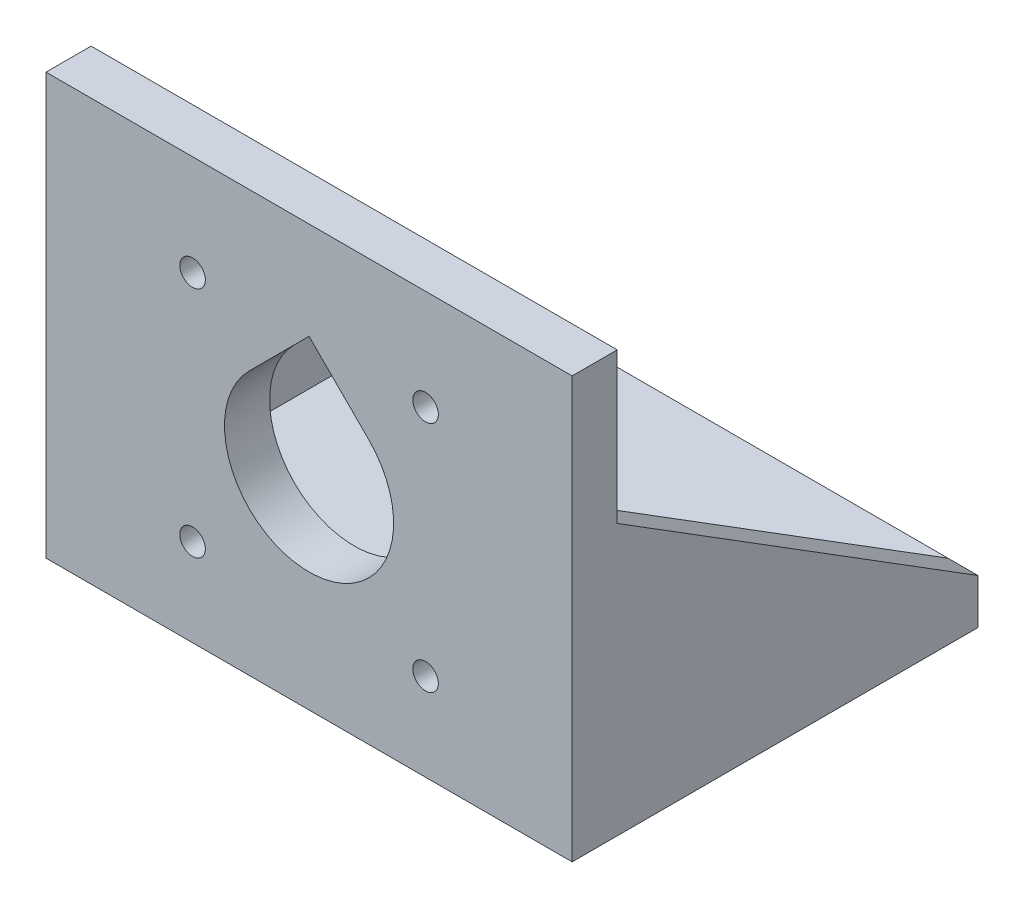
SolidWorks part; units mm, degrees
ref_plane "Спереди" through (0, 0, 0) normal (0, 0, 1) x (1, 0, 0)
ref_plane "Сверху" through (0, 0, 0) normal (0, 1, 0) x (1, 0, 0)
ref_plane "Справа" through (0, 0, 0) normal (1, 0, 0) x (0, 0, -1)
other "Configuration Table"
sketch "01_Пластина_эскиз" plane through (0, 0, 0) normal (0, 0, 1) x (1, 0, 0)
  line L1 (0, 0) -> (70, 0)
  line L2 (0, 0) -> (0, 56)
  line L3 (0, 56) -> (70, 56)
  line L4 (70, 0) -> (70, 56)
  dimension "D1" = 70
  dimension "D2" = 56
extrude "01_Передняя_пластина" add sketch "01_Пластина_эскиз" along normal blind 6
sketch "02_Полка_эскиз" plane through (0, 0, 0) normal (0, 1, 0) x (1, 0, 0)
  line L1 (0, 48) -> (70, 48)
  line L2 (0, 48) -> (0, -6)
  line L3 (0, -6) -> (70, -6)
  line L4 (70, 48) -> (70, -6)
  dimension "D1" = 70
  dimension "D2" = 54
  dimension "D3" = 6
extrude "02_Полка" add sketch "02_Полка_эскиз" along normal blind 6
sketch "03_Косынка_левая_эскиз" plane through (0, 0, 0) normal (1, 0, 0) x (0, 0, -1)
  line L0 (48, 6) -> (0, 6)
  line L1 (0, 6) -> (0, 36)
  line L2 (0, 36) -> (48, 6)
  dimension "D3" = 6
  dimension "D1" = 48
  dimension "D2" = 30
extrude "03_Косынка_левая" add sketch "03_Косынка_левая_эскиз" along normal blind 4
sketch "04_Косынка_правая_эскиз" plane through (0, 0, 0) normal (1, 0, 0) x (0, 0, -1)
  line L0 (48, 6) -> (0, 6)
  line L1 (0, 6) -> (0, 36)
  line L2 (0, 36) -> (48, 6)
  dimension "D3" = 6
  dimension "D1" = 48
  dimension "D2" = 30
extrude "04_Косынка_правая" add sketch "04_Косынка_правая_эскиз" along normal blind 4 from offset 66
sketch "05_Мотор_передний_фланец_эскиз" plane through (0, 0, 0) normal (0, 0, 1) x (1, 0, 0)
  line L0 (4, 6) -> (66, 6) construction
  circle A0 centre (35, 27.15) radius 11.25
  circle A1 centre (19.5, 11.65) radius 1.7
  circle A2 centre (19.5, 42.65) radius 1.7
  circle A3 centre (50.5, 11.65) radius 1.7
  circle A4 centre (50.5, 42.65) radius 1.7
  dimension "D1" = 3.4
  dimension "D2" = 3.4
  dimension "D3" = 3.4
  dimension "D4" = 3.4
  dimension "D5" = 22.5
  dimension "D6" = 15.5
  dimension "D7" = 31
  dimension "D8" = 15.5
  dimension "D9" = 31
  dimension "D10" = 35
  dimension "D11" = 21.15
extrude "05_Буртик_и_4_отверстия_М3" cut sketch "05_Мотор_передний_фланец_эскиз" against normal through all and the other way through all
sketch "06_Свод_45град_эскиз" plane through (0, 0, 0) normal (0, 0, 1) x (1, 0, 0)
  line L0 (27.045, 35.105) -> (42.955, 35.105)
  line L1 (42.955, 35.105) -> (35, 43.0599)
  line L2 (35, 43.0599) -> (27.045, 35.105)
  circle A0 centre (35, 27.15) radius 11.25 construction
  point P4 (26.9318, 34.9901)
  dimension "D1" = 7.955
  dimension "D2" = 15.9099
  dimension "D3" = 7.955
  dimension "D4" = 35
extrude "06_Свод_отверстия_для_печати" cut sketch "06_Свод_45град_эскиз" against normal through all and the other way through all
sketch "07_Крепление_полки_эскиз" plane through (0, 0, 0) normal (0, 1, 0) x (1, 0, 0)
  circle A0 centre (8.5, 12) radius 2.25
  circle A1 centre (8.5, 38) radius 2.25
  circle A2 centre (61.5, 12) radius 2.25
  circle A3 centre (61.5, 38) radius 2.25
  dimension "D1" = 4.5
  dimension "D2" = 4.5
  dimension "D3" = 4.5
  dimension "D4" = 4.5
  dimension "D5" = 53
  dimension "D6" = 26
  dimension "D7" = 8.5
  dimension "D8" = 12
extrude "07_4_отверстия_М4" cut sketch "07_Крепление_полки_эскиз" against normal through all and the other way through all
equation "\"Ширина\"= 70"
equation "\"Высота пластины\"= 56"
equation "\"Толщина стенок\"= 6"
equation "\"Длина полки\"= 48"
equation "\"Толщина косынки\"= 4"
equation "\"Высота косынки\"= 30"
equation "\"Высота оси\"= 30"
equation "\"Шаг М3 ПРЕДВ\"= 31"
equation "\"Отверстие буртика\"= 22.5"
equation "\"Отверстия М3\"= 3.4"
equation "\"Отверстия М4\"= 4.5"
equation "\"Отступ М4 сбоку\"= 8.5"
equation "\"Ближний ряд М4\"= 12"
equation "\"Отступ М4 сзади\"= 10"
equation "\"D1@01_Пластина_эскиз\" = \"Ширина\""
equation "\"D2@01_Пластина_эскиз\" = \"Высота пластины\""
equation "\"D1@01_Передняя_пластина\" = \"Толщина стенок\""
equation "\"D1@02_Полка_эскиз\" = \"Ширина\""
equation "\"D2@02_Полка_эскиз\" = \"Длина полки\" + \"Толщина стенок\""
equation "\"D1@02_Полка\" = \"Толщина стенок\""
equation "\"D1@03_Косынка_левая_эскиз\" = \"Длина полки\""
equation "\"D2@03_Косынка_левая_эскиз\" = \"Высота косынки\""
equation "\"D1@03_Косынка_левая\" = \"Толщина косынки\""
equation "\"D1@04_Косынка_правая_эскиз\" = \"Длина полки\""
equation "\"D2@04_Косынка_правая_эскиз\" = \"Высота косынки\""
equation "\"D1@04_Косынка_правая\" = \"Толщина косынки\""
equation "\"D19@04_Косынка_правая\" = \"Ширина\" - \"Толщина косынки\""
equation "\"D1@05_Мотор_передний_фланец_эскиз\" = \"Отверстия М3\""
equation "\"D2@05_Мотор_передний_фланец_эскиз\" = \"Отверстия М3\""
equation "\"D3@05_Мотор_передний_фланец_эскиз\" = \"Отверстия М3\""
equation "\"D4@05_Мотор_передний_фланец_эскиз\" = \"Отверстия М3\""
equation "\"D5@05_Мотор_передний_фланец_эскиз\" = \"Отверстие буртика\""
equation "\"D6@05_Мотор_передний_фланец_эскиз\" = \"Шаг М3 ПРЕДВ\" / 2"
equation "\"D7@05_Мотор_передний_фланец_эскиз\" = \"Шаг М3 ПРЕДВ\""
equation "\"D8@05_Мотор_передний_фланец_эскиз\" = \"Шаг М3 ПРЕДВ\" / 2"
equation "\"D9@05_Мотор_передний_фланец_эскиз\" = \"Шаг М3 ПРЕДВ\""
equation "\"D1@06_Свод_45град_эскиз\" = \"Отверстие буртика\" / (2 * SQR(2))"
equation "\"D2@06_Свод_45град_эскиз\" = \"Отверстие буртика\" / SQR(2)"
equation "\"D3@06_Свод_45град_эскиз\" = \"Отверстие буртика\" / (2 * SQR(2))"
equation "\"D1@07_Крепление_полки_эскиз\" = \"Отверстия М4\""
equation "\"D2@07_Крепление_полки_эскиз\" = \"Отверстия М4\""
equation "\"D3@07_Крепление_полки_эскиз\" = \"Отверстия М4\""
equation "\"D4@07_Крепление_полки_эскиз\" = \"Отверстия М4\""
equation "\"D5@07_Крепление_полки_эскиз\" = \"Ширина\" - 2 * \"Отступ М4 сбоку\""
equation "\"D6@07_Крепление_полки_эскиз\" = \"Длина полки\" - \"Ближний ряд М4\" - \"Отступ М4 сзади\""
equation "\"D3@02_Полка_эскиз\" = \"Толщина стенок\""
equation "\"D3@03_Косынка_левая_эскиз\" = \"Толщина стенок\""
equation "\"D3@04_Косынка_правая_эскиз\" = \"Толщина стенок\""
equation "\"D10@05_Мотор_передний_фланец_эскиз\" = \"Ширина\" / 2"
equation "\"D4@06_Свод_45град_эскиз\" = \"Ширина\" / 2"
equation "\"D7@07_Крепление_полки_эскиз\" = \"Отступ М4 сбоку\""
equation "\"D8@07_Крепление_полки_эскиз\" = \"Ближний ряд М4\""
